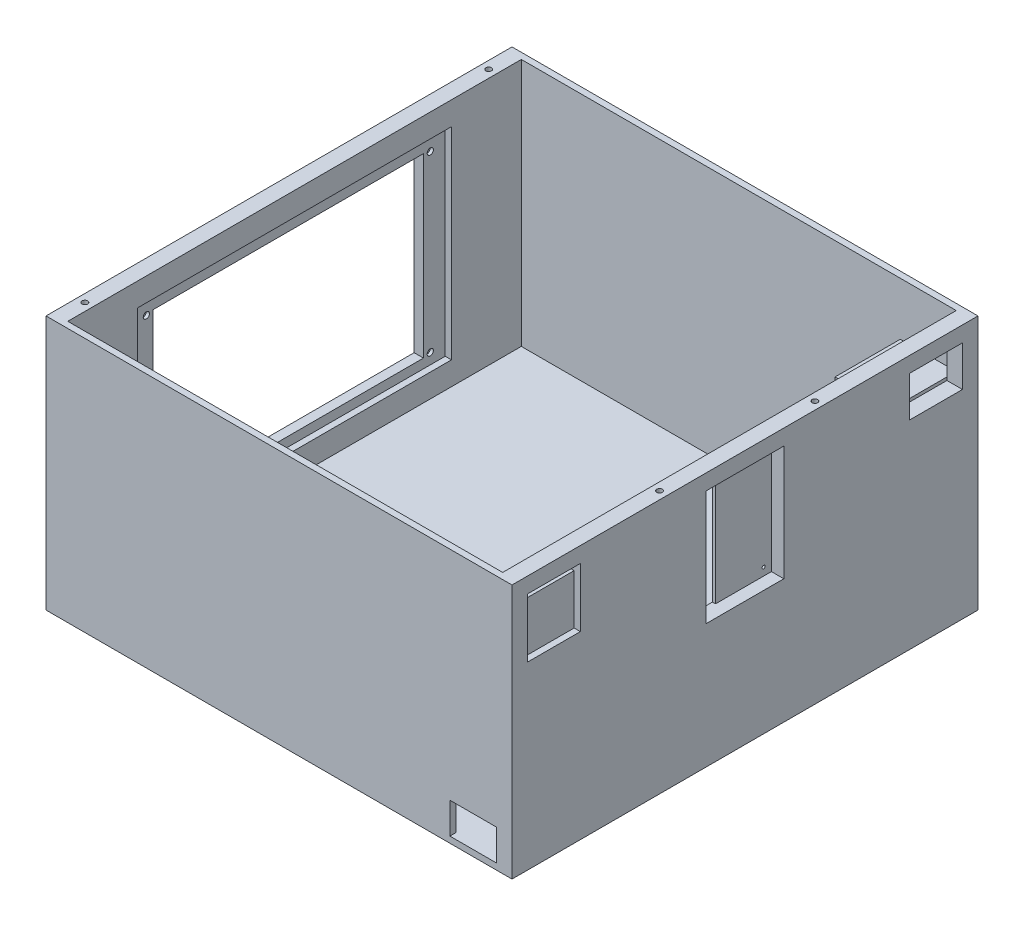
SolidWorks part; units mm, degrees
ref_plane "Ebene vorne" through (0, 0, 0) normal (0, 0, 1) x (1, 0, 0)
ref_plane "Ebene oben" through (0, 0, 0) normal (0, 1, 0) x (1, 0, 0)
ref_plane "Ebene rechts" through (0, 0, 0) normal (1, 0, 0) x (0, 0, -1)
sketch "Skizze1" plane through (0, 0, 0) normal (0, 1, 0) x (1, 0, 0)
  line L0 (-75.7337, 48.4968) -> (-70.7337, 48.4968)
  line L1 (-75.7337, 107.0584) -> (74.2663, 107.0584)
  line L2 (-75.7337, 107.0584) -> (-75.7337, -42.9416)
  line L3 (-75.7337, -42.9416) -> (74.2663, -42.9416)
  line L4 (74.2663, 107.0584) -> (74.2663, -42.9416)
  line L5 (-70.7337, 105.0584) -> (69.2663, 105.0584)
  line L6 (-70.7337, 105.0584) -> (-70.7337, -40.9416)
  line L7 (-70.7337, -40.9416) -> (69.2663, -40.9416)
  line L8 (69.2663, 105.0584) -> (69.2663, -40.9416)
  line L9 (-15.6556, -40.9416) -> (-15.6556, -42.9416)
  line L10 (69.2663, 56.8029) -> (74.2663, 56.8029)
extrude "Aufsatz-Linear austragen1" add sketch "Skizze1" against normal blind 2 contours L9 L7 L6 L0 L2 L3 | L8 L5 L6 L7 | L2 L3 L4 L1 | L6 L5 L8 L7 region at (-73.2337, 0, -47.4027) region at (-0.7337, 0, -32.0584)
extrude "Aufsatz-Linear austragen2" add sketch "Skizze1<3>" along normal blind 80 contours L8 L10 L4 L1 L2 L0 L6 L5 | L10 L8 L7 L9 L3 L4 | L9 L7 L6 L0 L2 L3 region at (-74.1234, 0, -77.7776) region at (-73.2337, 0, -47.4027) region at (-14.3127, 0, 41.9416)
sketch "Skizze1<3>" plane through (0, 0, 0) normal (0, 1, 0) x (1, 0, 0) same geometry as "Skizze1"
sketch "Skizze2" plane through (-75.7337, 0, 0) normal (-1, 0, 0) x (0, 0, 1)
  line L0 (-107.0584, 80) -> (42.9416, -2)
  line L1 (42.9416, -2) -> (42.9416, 80)
  line L2 (42.9416, 80) -> (-107.0584, -2)
  line L4 (11.4416, 10.5) -> (-75.5584, 10.5)
  line L5 (11.4416, 10.5) -> (11.4416, 67.5)
  line L6 (11.4416, 67.5) -> (-75.5584, 67.5)
  line L7 (-75.5584, 10.5) -> (-75.5584, 67.5)
  line L8 (11.4416, 10.5) -> (-75.5584, 67.5) construction
  line L9 (11.4416, 67.5) -> (-75.5584, 10.5) construction
  point P4 (-32.0584, 39)
extrude "Schnitt-Linear austragen1" cut sketch "Skizze2" against normal blind 10 contours L7 L0 L2 L5 L6 | L7 L2 L0 | L7 L4 L5 L0 L2 | L0 L5 L2 region at (-75.7337, 57.7765, -32.0584) region at (-75.7337, 39, -61.0584) region at (-75.7337, 39, -3.0584) region at (-75.7337, 20.2235, -32.0584)
sketch "Skizze5" plane through (74.2663, 0, 0) normal (1, 0, 0) x (0, 0, -1)
  line L0 (107.0584, 80) -> (8.1159, 80)
  line L2 (102.0584, 75) -> (85.0584, 75)
  line L3 (102.0584, 75) -> (102.0584, 62)
  line L4 (107.0584, -2) -> (107.0584, 80)
  line L5 (107.0584, -2) -> (25.0584, -2)
  line L6 (107.0584, -2) -> (-42.9416, -2) construction
  line L7 (25.0584, -2) -> (107.0584, 80)
  line L8 (102.0584, 75) -> (102.0584, 80)
  line L9 (102.0584, 62) -> (85.0584, 62)
  line L10 (85.0584, 75) -> (85.0584, 62)
extrude "Schnitt-Linear austragen3" cut sketch "Skizze5" against normal blind 10 contours L3 L2 L10 L9
sketch "Skizze6" plane through (74.2663, 0, 0) normal (1, 0, 0) x (0, 0, -1)
  line L0 (-42.9416, 80) -> (-42.9416, 75)
  line L1 (-42.9416, -2) -> (-42.9416, 80) construction
  line L4 (-37.9416, 75) -> (-20.9416, 75)
  line L5 (-37.9416, 75) -> (-37.9416, 56)
  line L6 (-37.9416, 56) -> (-20.9416, 56)
  line L7 (-20.9416, 75) -> (-20.9416, 56)
extrude "Schnitt-Linear austragen4" cut sketch "Skizze6" against normal blind 2 contours L5 L4 L7 L6
sketch "Skizze7" plane through (72.2663, 0, 0) normal (1, 0, 0) x (0, 0, -1)
  line L0 (-20.9416, 75) -> (-20.9416, 56) construction
  line L1 (-37.9416, 75) -> (-20.9416, 75)
  line L2 (-37.9416, 75) -> (-37.9416, 72)
  line L3 (-37.9416, 72) -> (-20.9416, 72)
  line L4 (-20.9416, 75) -> (-20.9416, 72)
extrude "Schnitt-Linear austragen5" cut sketch "Skizze7" against normal blind 10 contours L2 L1 L4 L3
sketch "Skizze9" plane through (0, 0, 0) normal (0, 1, 0) x (1, 0, 0)
  line L1 (69.2663, 105.0584) -> (51.2663, 105.0584)
  line L2 (69.2663, 105.0584) -> (69.2663, 84.0584)
  line L3 (69.2663, 84.0584) -> (51.2663, 84.0584)
  line L4 (51.2663, 105.0584) -> (51.2663, 84.0584)
extrude "Aufsatz-Linear austragen3" add sketch "Skizze9" along normal blind 63 contours L2 L1 L4 L3
sketch "Skizze10" plane through (0, 0, 40.9416) normal (0, 0, -1) x (-1, 0, 0)
  line L1 (-69.2663, 0) -> (-54.2663, 0)
  line L2 (-69.2663, 0) -> (-69.2663, 10)
  line L3 (-69.2663, 10) -> (-54.2663, 10)
  line L4 (-54.2663, 0) -> (-54.2663, 10)
extrude "Schnitt-Linear austragen6" cut sketch "Skizze10" against normal blind 63 contours L2 L1 L4 L3
sketch "Skizze11" plane through (-70.7337, 0, 0) normal (1, 0, 0) x (0, 0, -1)
  line L0 (-40.9416, 80) -> (105.0584, 0)
  line L1 (105.0584, 0) -> (105.0584, 80)
  line L2 (105.0584, 80) -> (-40.9416, 0)
  line L3 (-18.4416, 7.5) -> (-18.4416, 72.5)
  line L4 (-18.4416, 7.5) -> (82.5584, 7.5)
  line L5 (-18.4416, 72.5) -> (82.5584, 72.5)
  line L6 (82.5584, 7.5) -> (82.5584, 72.5)
  line L7 (-18.4416, 7.5) -> (82.5584, 72.5) construction
  line L8 (-18.4416, 72.5) -> (82.5584, 7.5) construction
  point P9 (32.0584, 40)
  line M9 (-11.4416, 67.5) -> (75.5584, 67.5)
  line M10 (75.5584, 67.5) -> (75.5584, 10.5)
  line M11 (75.5584, 10.5) -> (-11.4416, 10.5)
  line M12 (-11.4416, 10.5) -> (-11.4416, 67.5)
extrude "Schnitt-Linear austragen7" cut sketch "Skizze11" against normal blind 2 contours L0 L2 M12 M11 M10 | L2 L0 M10 | L2 L0 M10 M9 M12 | L2 L0 M12 | L3 L2 L0 M12 | L2 L6 L5 L3 L0 M12 M9 M10 | L0 L6 L2 M10 | L4 L6 L0 L2 L3 M10 M11 M12 region at (-70.7337, 69.828, -32.0584) region at (-70.7337, 40, 15.0285) region at (-70.7337, 58.1897, -32.0584) region at (-70.7337, 40, -3.0584) region at (-70.7337, 9.5219, -32.0584) region at (-70.7337, 40, -61.0584) region at (-70.7337, 20.6375, -32.0584) region at (-70.7337, 40, -79.1453)
sketch "Skizze17" plane through (-72.7337, 0, 0) normal (1, 0, 0) x (0, 0, -1)
  line L0 (-11.4416, 67.5) -> (75.5584, 10.5)
  line L3 (75.5584, 10.5) -> (75.5584, 67.5)
  line L4 (75.5584, 67.5) -> (-11.4416, 10.5)
  line L5 (32.0584, 11) -> (32.0584, 67)
  line L6 (-13.6416, 67) -> (77.7584, 67)
  line L8 (-13.6416, 11) -> (77.7584, 11)
  circle A0 centre (77.7584, 67) radius 1
  circle A1 centre (77.7584, 11) radius 1
  circle A2 centre (-13.6416, 11) radius 1
  circle A3 centre (-13.6416, 67) radius 1
  point P9 (32.0584, 39)
  point P10 (32.0584, 67)
  point P12 (32.0584, 67)
  point P14 (32.0584, 11)
extrude "Schnitt-Linear austragen10" cut sketch "Skizze17" against normal blind 1 contours A3 | A0 | A1 | A2
sketch "Skizze18" plane through (-75.7337, 0, 0) normal (-1, 0, 0) x (0, 0, 1)
  line L0 (11.4416, 67.5) -> (42.9416, 67.5)
  line L1 (42.9416, -2) -> (42.9416, 80) construction
  line L2 (27.1916, 67.5) -> (27.1916, 57.5)
  line L3 (27.1916, 57.5) -> (27.1916, 47.5)
  line L4 (27.1916, 47.5) -> (27.1916, 37.5)
  line L5 (27.1916, 37.5) -> (27.1916, 27.5)
  line L6 (-75.5584, 67.5) -> (-107.0584, 67.5)
  line L7 (30.6916, 54) -> (23.6916, 54)
  line L8 (30.6916, 54) -> (30.6916, 61)
  line L9 (30.6916, 61) -> (23.6916, 61)
  line L10 (23.6916, 54) -> (23.6916, 61)
  line L11 (30.6916, 54) -> (23.6916, 61) construction
  line L12 (30.6916, 61) -> (23.6916, 54) construction
  line L13 (30.6916, 44) -> (23.6916, 44)
  line L14 (30.6916, 44) -> (30.6916, 51)
  line L15 (30.6916, 51) -> (23.6916, 51)
  line L16 (23.6916, 44) -> (23.6916, 51)
  line L17 (30.6916, 44) -> (23.6916, 51) construction
  line L18 (30.6916, 51) -> (23.6916, 44) construction
  line L19 (30.6916, 34) -> (23.6916, 34)
  line L20 (30.6916, 34) -> (30.6916, 41)
  line L21 (30.6916, 41) -> (23.6916, 41)
  line L22 (23.6916, 34) -> (23.6916, 41)
  line L23 (30.6916, 34) -> (23.6916, 41) construction
  line L24 (30.6916, 41) -> (23.6916, 34) construction
  line L25 (30.6916, 24) -> (23.6916, 24)
  line L26 (30.6916, 24) -> (30.6916, 31)
  line L27 (30.6916, 31) -> (23.6916, 31)
  line L28 (23.6916, 24) -> (23.6916, 31)
  line L29 (30.6916, 24) -> (23.6916, 31) construction
  line L30 (30.6916, 31) -> (23.6916, 24) construction
  line L31 (-107.0584, -2) -> (-107.0584, 80) construction
  line L33 (-88.0184, 54) -> (-95.0184, 54)
  line L34 (-88.0184, 54) -> (-88.0184, 61)
  line L35 (-88.0184, 61) -> (-95.0184, 61)
  line L36 (-95.0184, 54) -> (-95.0184, 61)
  line L37 (-88.0184, 54) -> (-95.0184, 61) construction
  line L38 (-88.0184, 61) -> (-95.0184, 54) construction
  line L39 (-88.0184, 44) -> (-95.0184, 44)
  line L40 (-88.0184, 44) -> (-88.0184, 51)
  line L41 (-88.0184, 51) -> (-95.0184, 51)
  line L42 (-95.0184, 44) -> (-95.0184, 51)
  line L43 (-88.0184, 44) -> (-95.0184, 51) construction
  line L44 (-88.0184, 51) -> (-95.0184, 44) construction
  line L45 (-88.0184, 34) -> (-95.0184, 34)
  line L46 (-88.0184, 34) -> (-88.0184, 41)
  line L47 (-88.0184, 41) -> (-95.0184, 41)
  line L48 (-95.0184, 34) -> (-95.0184, 41)
  line L49 (-88.0184, 34) -> (-95.0184, 41) construction
  line L50 (-88.0184, 41) -> (-95.0184, 34) construction
  line L51 (-88.0184, 24) -> (-95.0184, 24)
  line L52 (-88.0184, 24) -> (-88.0184, 31)
  line L53 (-88.0184, 31) -> (-95.0184, 31)
  line L54 (-95.0184, 24) -> (-95.0184, 31)
  line L55 (-88.0184, 24) -> (-95.0184, 31) construction
  line L56 (-88.0184, 31) -> (-95.0184, 24) construction
  point P31 (-91.5184, 57.5)
  point P33 (-91.5184, 47.5)
  point P41 (-91.5184, 37.5)
  point P46 (-91.5184, 27.5)
extrude "Schnitt-Linear austragen11" cut sketch "Skizze18" against normal blind 4.5 contours L10 L7 L3 L2 L9 | L8 L9 L2 L3 L7 | L14 L15 L3 L4 L13 | L16 L13 L4 L3 L15 | L22 L19 L5 L4 L21 | L20 L21 L4 L5 L19 | L28 L25 L26 L27 | L36 L33 L34 L35 | L42 L39 L40 L41 | L48 L45 L46 L47 | L54 L51 L52 L53 region at (-75.7337, 57.5, 28.9416) region at (-75.7337, 30.901, 28.9416) region at (-75.7337, 37.5, 28.9416) region at (-75.7337, 37.5, 25.4416) region at (-75.7337, 47.5, 28.9416) region at (-75.7337, 47.5, 25.4416) region at (-75.7337, 57.5, 25.4416) region at (-75.7337, 57.5, -91.5184) region at (-75.7337, 47.5, -91.5184) region at (-75.7337, 37.5, -91.5184) region at (-75.7337, 27.5, -91.5184)
sketch "Skizze19" plane through (0, 80, 0) normal (0, 1, 0) x (1, 0, 0)
  line L0 (-75.7337, -32.9416) -> (-70.7337, -32.9416)
  line L1 (-75.7337, 107.0584) -> (-75.7337, -42.9416) construction
  line L2 (-70.7337, 105.0584) -> (-70.7337, -40.9416) construction
  line L3 (-71.9209, -32.9416) -> (-71.9209, -42.9416)
  line L4 (-75.7337, -42.9416) -> (74.2663, -42.9416) construction
  line L5 (-73.2337, 107.0584) -> (-73.2337, 97.0584)
  line L6 (-75.7337, 107.0584) -> (74.2663, 107.0584) construction
  line L7 (-75.7337, 97.0584) -> (-70.7337, 97.0584)
  line L8 (71.7663, 7.0584) -> (71.7663, -42.9416)
  line L9 (69.2663, 7.0584) -> (74.2663, 7.0584)
  line L10 (69.2663, 105.0584) -> (69.2663, -40.9416) construction
  line L11 (74.2663, 107.0584) -> (74.2663, -42.9416) construction
  line L12 (71.7663, 57.0584) -> (71.7663, 107.0584)
  line L13 (69.2663, 57.0584) -> (74.2663, 57.0584)
  circle A0 centre (-73.2337, -32.9416) radius 0.9
  circle A1 centre (-73.2337, 97.0584) radius 0.9
  circle A3 centre (71.7663, 57.0584) radius 0.9
  circle A4 centre (71.7663, 7.0584) radius 0.9
extrude "Schnitt-Linear austragen12" cut sketch "Skizze19" against normal blind 15 contours L8 A4 L9 | L9 A4 L8 | L9 A4 | A3 | A0 | A1 region at (72.1483, 80, -6.6764) region at (71.7663, 80, -7.4403) region at (71.3843, 80, -6.6764)
sketch "Skizze20" plane through (74.2663, 0, 0) normal (1, 0, 0) x (0, 0, -1)
  line L0 (-42.9416, 75) -> (107.0584, 75)
  line L1 (-42.9416, -2) -> (-42.9416, 80) construction
  line L2 (107.0584, -2) -> (107.0584, 80) construction
  line L3 (19.5584, 37.977) -> (19.5584, 74.977)
  line L4 (19.5584, 37.977) -> (44.5584, 37.977)
  line L5 (19.5584, 74.977) -> (44.5584, 74.977)
  line L6 (44.5584, 37.977) -> (44.5584, 74.977)
  line L7 (19.5584, 37.977) -> (44.5584, 74.977) construction
  line L8 (19.5584, 74.977) -> (44.5584, 37.977) construction
  point P7 (32.0584, 75)
  point P8 (0, 0)
  point P9 (32.0584, 56.477)
  point P10 (0, 0)
  point P11 (32.0584, 58.9924)
extrude "Schnitt-Linear austragen13" cut sketch "Skizze20" against normal blind 4 contours L3 L4 L6 L5
sketch "Skizze21" plane through (70.2663, 0, 0) normal (1, 0, 0) x (0, 0, -1)
  line L0 (19.5584, 37.977) -> (44.5584, 37.977) construction
  line L1 (19.5584, 74.977) -> (26.5584, 74.977)
  line L2 (19.5584, 74.977) -> (19.5584, 37.977)
  line L3 (19.5584, 37.977) -> (26.5584, 37.977)
  line L4 (26.5584, 74.977) -> (26.5584, 37.977)
extrude "Schnitt-Linear austragen14" cut sketch "Skizze21" against normal blind 3 contours L2 L1 L4 L3
sketch "Skizze24" plane through (70.2663, 0, 0) normal (1, 0, 0) x (0, 0, -1)
  line L0 (44.5584, 40.477) -> (42.0584, 40.477)
  line L1 (44.5584, 37.977) -> (44.5584, 74.977) construction
  line L2 (42.0584, 40.477) -> (42.0584, 37.977)
  line L3 (26.5584, 37.977) -> (44.5584, 37.977) construction
  circle A0 centre (42.0584, 40.477) radius 0.5
extrude "Schnitt-Linear austragen15" cut sketch "Skizze24" against normal blind 6 contours L0 A0 L2 | L2 A0 L0 region at (70.2663, 40.2648, -42.2706) region at (70.2663, 40.5477, -41.9876)
